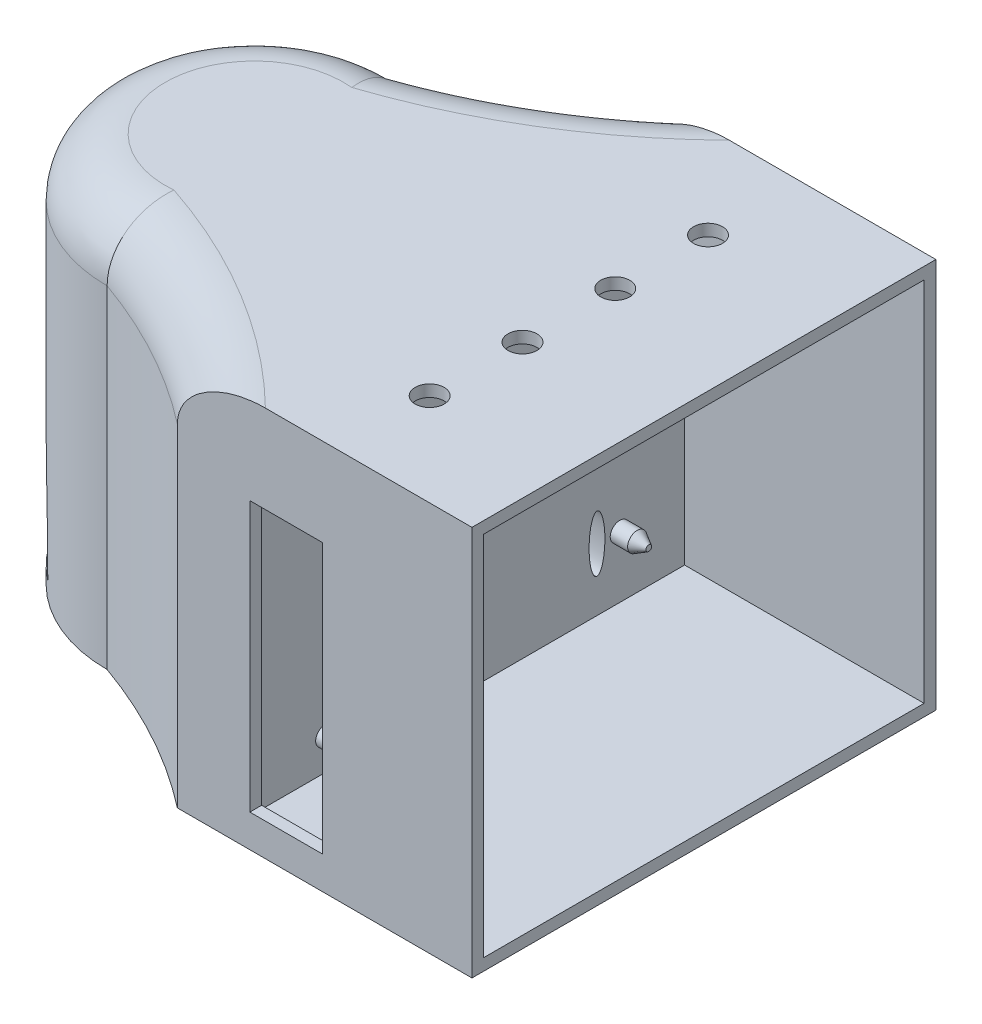
SolidWorks part; units mm, degrees
ref_plane "Front" through (0, 0, 0) normal (0, 0, 1) x (1, 0, 0)
ref_plane "Top" through (0, 0, 0) normal (0, 1, 0) x (1, 0, 0)
ref_plane "Right" through (0, 0, 0) normal (1, 0, 0) x (0, 0, -1)
sketch "Sketch1" plane through (0, 0, 0) normal (0, 1, 0) x (1, 0, 0)
  line L1 (-22.2874, 26.8069) -> (28.5126, 26.8069)
  line L2 (-22.2874, 26.8069) -> (-22.2874, -53.2031)
  line L3 (-22.2874, -53.2031) -> (28.5126, -53.2031)
  line L4 (28.5126, 26.8069) -> (28.5126, -53.2031)
  circle A0 centre (-49.0165, -13.1981) radius 25.4
  arc A1 (-49.0165, 12.2019) -> (-22.2874, 26.8069) centre (-80.7565, 102.0516) ccw
  arc A2 (-22.2874, -53.2031) -> (-49.0165, -38.5981) centre (-80.7565, -128.4478) ccw
  point P7 (-22.2874, -13.1981)
  dimension "D3" = 50.8
  dimension "D1" = 80.01
  dimension "D2" = 50.8
extrude "Boss-Extrude2" add sketch "Sketch1" along normal blind 67.31 contours A0 | A2 L2 A1 A0 | L4 L1 L2 L3 region at (3.1126, 0, 13.1981) region at (-23.131, 0, 13.1981) region at (-49.0165, 0, 13.1981)
fillet "Fillet1" radius 10 3 edges at (-35.0646, 67.31, 44.8257) (-74.4165, 67.31, 13.1981) (-35.0646, 67.31, -18.4296)
sketch "Sketch2" plane through (28.5126, 0, 0) normal (1, 0, 0) x (0, 0, -1)
  line L0 (26.8069, 67.31) -> (26.8069, 0) construction
  line L1 (-51.1711, 65.278) -> (24.7749, 65.278)
  line L2 (-51.1711, 65.278) -> (-51.1711, 2.032)
  line L3 (-51.1711, 2.032) -> (24.7749, 2.032)
  line L4 (24.7749, 65.278) -> (24.7749, 2.032)
  line L5 (26.8069, 0) -> (-53.2031, 0) construction
  line L6 (26.8069, 67.31) -> (-53.2031, 67.31) construction
  line L7 (-53.2031, 57.31) -> (-53.2031, 0) construction
  dimension "D1" = 2.032
  dimension "D2" = 2.032
  dimension "D3" = 2.032
  dimension "D4" = 2.032
extrude "Cut-Extrude1" cut sketch "Sketch2" against normal blind 41.31
sketch "Sketch3" plane through (-12.7974, 0, 0) normal (1, 0, 0) x (0, 0, -1)
  line L0 (-51.1711, 65.278) -> (-51.1711, 2.032) construction
  line L1 (-37.2011, 55.8247) -> (13.5989, 55.8247)
  line L2 (-37.2011, 55.8247) -> (-37.2011, 7.5647)
  line L3 (-37.2011, 7.5647) -> (13.5989, 7.5647)
  line L4 (13.5989, 55.8247) -> (13.5989, 7.5647)
  line L6 (-7.8992, 40.5847) -> (13.5989, 40.5847)
  line L7 (-7.8992, 40.5847) -> (-7.8992, 12.6447)
  line L8 (-7.8992, 12.6447) -> (13.5989, 12.6447)
  line L9 (13.5989, 40.5847) -> (13.5989, 12.6447)
  circle A0 centre (-37.2011, 55.8247) radius 1.651
  circle A1 centre (-37.2011, 7.5647) radius 1.651
  circle A2 centre (13.5989, 40.5847) radius 1.651
  circle A3 centre (13.5989, 12.6447) radius 1.651
  dimension "D4" = 3.302
  dimension "D1" = 50.8
  dimension "D2" = 48.26
  dimension "D3" = 13.97
  dimension "D5" = 27.94
  dimension "D6" = 15.24
extrude "Boss-Extrude3" add sketch "Sketch3" along normal blind 5 contours A0 | A2 | A3 | A1
chamfer "Chamfer1" distance 2 angle 30 4 edges at (-7.7974, 12.6447, -15.2499) (-7.7974, 40.5847, -15.2499) (-7.7974, 55.8247, 35.5501) (-7.7974, 7.5647, 35.5501) first distance on face at (-7.7974, 12.6447, -15.2499) first distance on face at (-7.7974, 40.5847, -15.2499) first distance on face at (-7.7974, 55.8247, 35.5501) first distance on face at (-7.7974, 7.5647, 35.5501)
ref_plane "Plane1" through (-76.2, 0, 0) normal (1, 0, 0) x (0, 0, -1)
sketch "Sketch4" plane through (-76.2, 0, 0) normal (1, 0, 0) x (0, 0, -1)
  line L0 (6.8907, 2.8887) -> (-33.2868, 2.8887)
  line L2 (-38.5981, 0) -> (12.2019, 0) construction
  ellipse E0 centre (-13.1981, 2.8887) end of major axis (-13.1981, 51.376) minor radius 20.0888 (-33.2868, 2.8887) -> (6.8907, 2.8887) cw
  point P6 (-13.1981, 0)
extrude "Cut-Extrude3" cut sketch "Sketch4" along normal blind 52
sketch "Sketch5" plane through (0, 0, 53.2031) normal (0, 0, 1) x (1, 0, 0)
  line L0 (-12.7974, 65.278) -> (-12.7974, 2.032) construction
  line L1 (-9.7974, 52.1466) -> (2.7256, 52.1466)
  line L2 (-9.7974, 52.1466) -> (-9.7974, 5.6244)
  line L3 (-9.7974, 5.6244) -> (2.7256, 5.6244)
  line L4 (2.7256, 52.1466) -> (2.7256, 5.6244)
  dimension "D1" = 3
ref_plane "Plane2" through (0, 0, 13.1981) normal (0, 0, 1) x (1, 0, 0)
sketch "Sketch7" plane through (0, 0, 13.1981) normal (0, 0, 1) x (1, 0, 0)
  line L1 (-43.6771, 18.927) -> (-24.6771, 18.927)
  line L2 (-43.6771, 18.927) -> (-43.6771, 6.927)
  line L3 (-43.6771, 6.927) -> (-24.6771, 6.927)
  line L4 (-24.6771, 18.927) -> (-24.6771, 6.927)
  dimension "D1" = 19
  dimension "D2" = 12
extrude "Cut-Extrude4" cut sketch "Sketch7" against normal blind 25 and the other way blind 25
sketch "Sketch8" plane through (-24.6771, 0, 0) normal (-1, 0, 0) x (0, 0, 1)
  ellipse E0 centre (-9.6654, 12.7751) end of major axis (-9.6654, 7.9051) minor radius 1.3674
  ellipse E1 centre (35.2422, 12.7751) end of major axis (35.2422, 7.9051) minor radius 1.3674
  point P12 (0, 0)
extrude "Cut-Extrude5" cut sketch "Sketch8" against normal through all
extrude "Cut-Extrude6" cut sketch "Sketch5" against normal blind 10
sketch "Sketch9" plane through (0, 67.31, 0) normal (0, 1, 0) x (1, 0, 0)
  line L0 (-7.1056, 26.8069) -> (28.5126, 26.8069) construction
  circle A0 centre (5.2107, -37.1931) radius 2.5
  circle A1 centre (5.2107, -21.1931) radius 2.5
  circle A2 centre (5.2107, -5.1931) radius 2.5
  circle A3 centre (5.2107, 10.8069) radius 2.5
  point P8 (0, 0)
  point P9 (0, 0)
  point P10 (21.9644, 6.6102)
  point P11 (22.5462, -7.881)
  point P12 (22.6942, -21.2088)
  point P13 (3.5348, -30.9382)
  point P14 (5.9777, -31.956)
  point P15 (5.3882, -35.4999)
  point P16 (5.2107, 8.922)
  point P17 (0, 0)
  point P18 (0, 0)
  dimension "D1" = 5
  dimension "D2" = 16
  dimension "D3" = 16
  dimension "D4" = 16
  dimension "D5" = 16
extrude "Cut-Extrude7" cut sketch "Sketch9" against normal blind 10 contours A0 | A1 | A2 | A3
